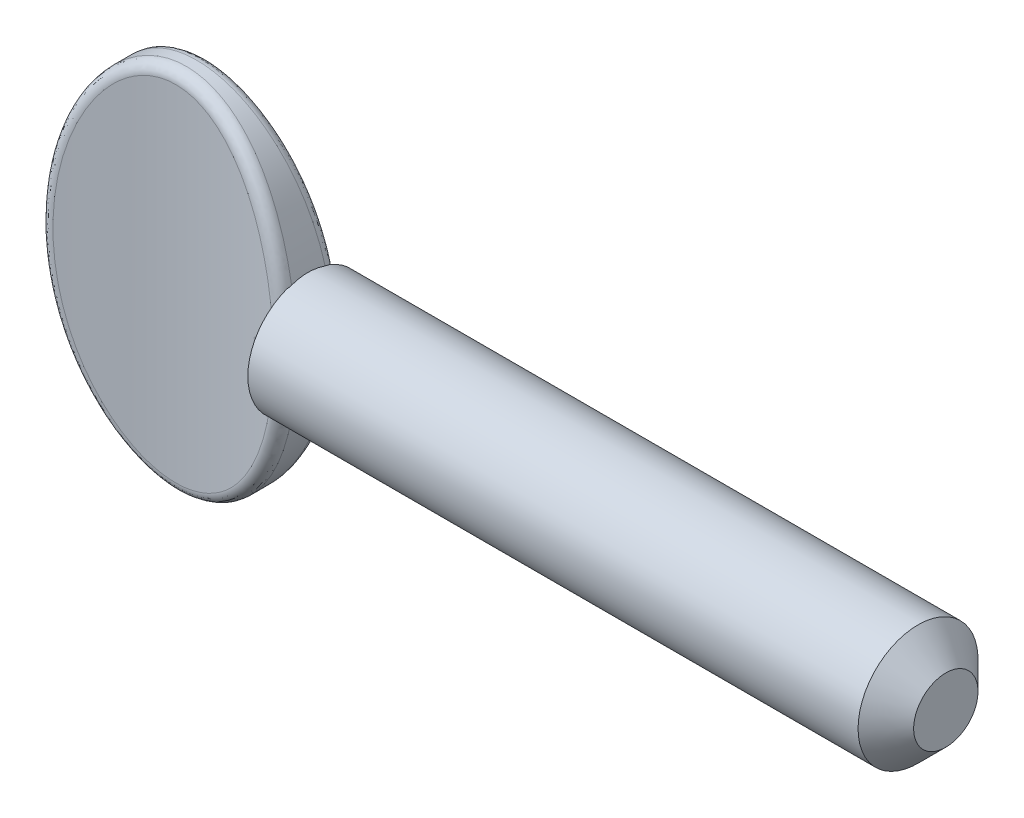
SolidWorks part; units mm, degrees
ref_plane "Front" through (0, 0, 0) normal (0, 0, 1) x (1, 0, 0)
ref_plane "Top" through (0, 0, 0) normal (0, 1, 0) x (1, 0, 0)
ref_plane "Right" through (0, 0, 0) normal (1, 0, 0) x (0, 0, -1)
ref_axis "Axis1" through (-50, 0, 0) along (1, 0, 0)
sketch "Sketch1" plane through (0, 0, 0) normal (0, 0, 1) x (1, 0, 0)
  line L0 (0, 0) -> (30.353, 0) construction
  line L1 (6.604, -2.413) -> (6.604, 2.413)
  line L2 (6.604, -2.413) -> (4.6797, -2.413) construction
  ellipse E0 centre (0, 0) end of major axis (0, -7.366) minor radius 4.953
  dimension "D2" = 1.651
  dimension "B" = 9.906
  dimension "L" = 25.4
extrude "Extrude1" add sketch "Sketch1" along normal mid plane 2.54
sketch "Sketch2" plane through (0, 0, 0) normal (0, 1, 0) x (1, 0, 0)
  line L0 (4.953, 1.27) -> (-4.953, 1.27) construction
  line L1 (0, 0) -> (0, 1.1721) construction
  line L2 (-1.7991, 0) -> (2.0444, 0) construction
  line L3 (-4.953, -1.27) -> (4.953, -1.27) construction
  line L6 (-4.953, 1.27) -> (-4.953, -1.27)
  line L7 (4.953, 1.27) -> (4.953, -1.27)
  arc A0 (-4.953, 1.27) -> (4.953, 1.27) centre (0, 20.2692) ccw
  arc A1 (-4.953, -1.27) -> (4.953, -1.27) centre (0, -20.2692) cw
extrude "Cut-Extrude1" cut sketch "Sketch2" against normal through all and the other way through all flip side to cut
fillet "Fillet3" radius 0.4233 2 edges at (-4.9097, -0.9722, 1.2588) (0.2064, 7.3596, -0.6361)
sketch "Sketch3" plane through (0, 0, 0) normal (0, 1, 0) x (1, 0, 0)
  line L0 (30.353, 0) -> (30.353, 1.2954)
  line L1 (0, 0) -> (21.0288, 0) construction
  line L2 (0, 0) -> (30.353, 0) construction
  line L3 (6.604, 2.413) -> (6.604, 0) construction
  line L4 (6.604, 2.413) -> (29.2354, 2.413)
  line L5 (30.353, 1.2954) -> (29.2354, 2.413)
  line L6 (6.604, 2.413) -> (4.6797, 2.413)
  line L7 (3.4459, 0.9397) -> (3.4459, 0)
  line L8 (4.6797, 0) -> (4.6797, 2.413) construction
  line L9 (3.4459, 0) -> (30.353, 0)
  arc A0 (4.6797, 2.413) -> (3.4459, 0.9397) centre (3.1832, 2.413) cw
  arc A3 (-4.953, 1.27) -> (4.953, 1.27) centre (0, 20.2692) ccw construction
  dimension "D1" = 45
revolve "Revolve1" add sketch "Sketch3" angle 360 about L0
cosmetic thread "Cosmetic Thread1" [suppressed]
sketch "Sketch4" plane through (0, 0, 0) normal (0, 0, 1) x (1, 0, 0)
  line L0 (0, 0) -> (27.7993, 0) construction
  line L1 (28.9626, 2.413) -> (29.2354, 1.9406)
  line L2 (29.2354, 1.9406) -> (29.5082, 2.413)
  line L3 (29.5082, 2.413) -> (29.5082, 2.9585)
  line L4 (29.5082, 2.9585) -> (28.9626, 2.9585)
  line L5 (28.9626, 2.9585) -> (28.9626, 2.413)
  line L6 (29.2354, 2.413) -> (29.2354, -2.413) construction
  dimension "D1" = 3.8811
  dimension "D2" = 4.826
revolve "Cut-Revolve10" [suppressed] cut sketch "Sketch4" angle 360 about L0
pattern_linear "LPattern10" [suppressed] count 31 along (-1, 0, 0) of bodies 109
equation "\"D2@Sketch1\" = \"B@Sketch1\" / 6"
equation "\"D1@Fillet3\" = \"C1@Sketch2\" / 3"
equation "\"DIA@Sketch3\" = \"D@Sketch1\""
equation "\"D1@Cosmetic Thread1\" = \"L@Sketch1\" -  ( \"D@Sketch1\" - \"flat_dia@Sketch3\" )  / 2"
equation "\"D1@Sketch4\" = \"D2@Cosmetic Thread1\""
equation "\"D2@Sketch4\" = \"DIA@Sketch3\""
equation "\"D1@LPattern10\" = \"D1@Cosmetic Thread1\" / \"P@LPattern10\" "
